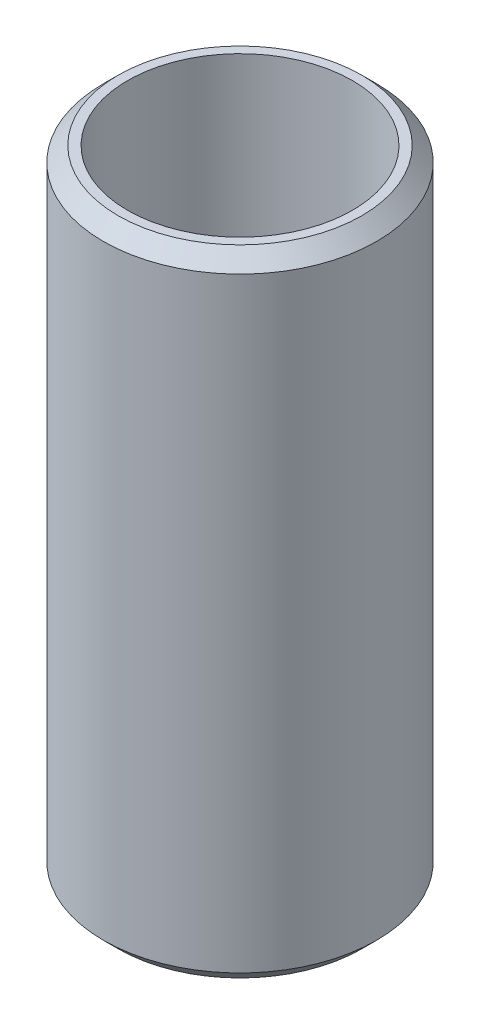
SolidWorks part; units mm, degrees
ref_plane "Front Plane" through (0, 0, 0) normal (0, 0, 1) x (1, 0, 0)
ref_plane "Top Plane" through (0, 0, 0) normal (0, 1, 0) x (1, 0, 0)
ref_plane "Right Plane" through (0, 0, 0) normal (1, 0, 0) x (0, 0, -1)
sketch "Sketch1" plane through (0, 0, 0) normal (0, 1, 0) x (1, 0, 0)
  circle A0 centre (0, 0) radius 42.5
  dimension "SHAFT_OD" = 85
extrude "Boss-Extrude1" add sketch "Sketch1" along normal blind 197.4855
sketch "Sketch2" plane through (0, 0, 0) normal (0, 1, 0) x (1, 0, 0)
  circle A0 centre (0, 0) radius 34.972
  dimension "BORE_D" = 69.9439
extrude "Cut-Extrude1" cut sketch "Sketch2" along normal through all
chamfer "Chamfer1" distance 4.6165 angle 45 2 edges at (0, 197.4855, 42.5) (0, 0, 42.5)
